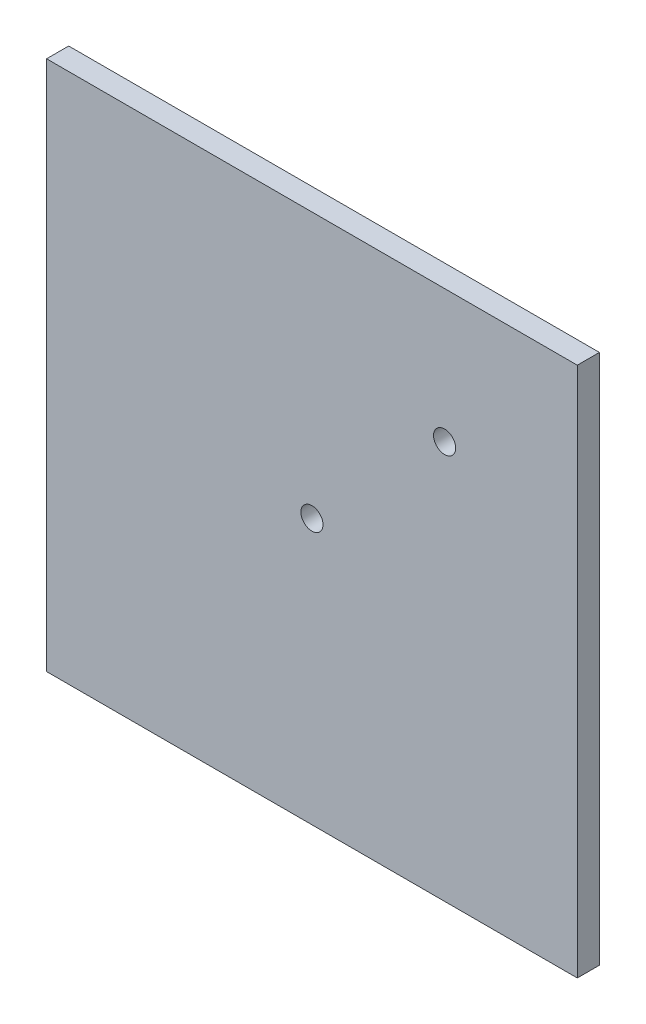
SolidWorks part; units mm, degrees
ref_plane "Front Plane" through (0, 0, 0) normal (0, 0, 1) x (1, 0, 0)
ref_plane "Top Plane" through (0, 0, 0) normal (0, 1, 0) x (1, 0, 0)
ref_plane "Right Plane" through (0, 0, 0) normal (1, 0, 0) x (0, 0, -1)
sketch "Sketch1" plane through (0, 0, 0) normal (0, 0, 1) x (1, 0, 0)
  line L1 (0, 0) -> (152.4, 0)
  line L2 (0, 0) -> (0, 152.4)
  line L3 (0, 152.4) -> (152.4, 152.4)
  line L4 (152.4, 0) -> (152.4, 152.4)
  circle A0 centre (76.2, 76.2) radius 3.175
  circle A1 centre (114.3, 114.3) radius 3.175
  dimension "D3" = 6.35
  dimension "D4" = 76.2
  dimension "D8" = 6.35
  dimension "D1" = 152.4
  dimension "D2" = 152.4
  dimension "D5" = 76.2
  dimension "D6" = 38.1
  dimension "D7" = 38.1
extrude "Boss-Extrude1" add sketch "Sketch1" along normal blind 6.35
